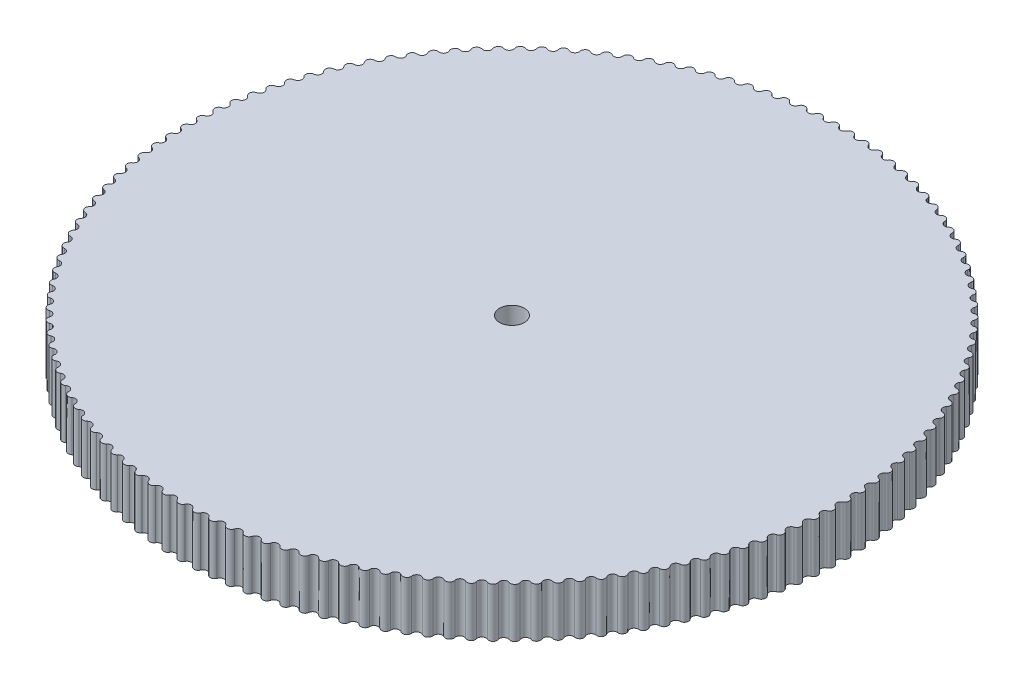
SolidWorks part; units mm, degrees
note: '?' marks a value the reader was unsure of.
ref_plane "Front Plane" through (0, 0, 0) normal (0, 0, 1) x (1, 0, 0)
ref_plane "Top Plane" through (0, 0, 0) normal (0, 1, 0) x (1, 0, 0)
ref_plane "Right Plane" through (0, 0, 0) normal (1, 0, 0) x (0, 0, -1)
sketch "Sketch1" plane through (0, 0, 0) normal (0, 1, 0) x (1, 0, 0)
  line L0 (0, 32.75) -> (0, 33.25) construction
  line L1 (0.7735, 32.7409) -> (0.7853, 33.2407) construction
  line L2 (1.5466, 32.7135) -> (1.5702, 33.2129) construction
  line L3 (0, 33) -> (0, 1.25)
  line L4 (0.059, 1.2486) -> (1.5584, 32.9632)
  circle A0 centre (0, 0) radius 32.75 construction
  arc A1 (0, 33) -> (0.7794, 32.9908) centre (0.3919, 33.1781) ccw
  arc A2 (1.5702, 33.2129) -> (0, 33.25) centre (0, 0) ccw construction
  arc A3 (0.7794, 32.9908) -> (1.5584, 32.9632) centre (1.1627, 32.8022) cw
  arc A4 (0.059, 1.2486) -> (0, 1.25) centre (0, 0) ccw
  point P6 (0, 33)
  point P9 (0.7794, 32.9908)
  dimension "D1" = 65.5
  dimension "D2" = 0.5
  dimension "D3" = 2.5
extrude "Boss-Extrude1" add sketch "Sketch1" along normal blind 5
pattern_circular "CirPattern1" count 133 over 360 about axis through (0, 0, 0) along (0, 1, 0) of "Boss-Extrude1"
ref_axis "Axis1" through (0, 0, 0) along (0, 1, 0)?
sketch "Sketch2" plane through (0, 5, 0) normal (0, 1, 0) x (1, 0, 0)
  line L0 (0, 74.1691) -> (0, -78.0459) construction
  line L1 (4.7625, 3.175) -> (6.6675, 3.175)
  line L2 (4.7625, 3.175) -> (4.7625, -3.175)
  line L3 (4.7625, -3.175) -> (6.6675, -3.175)
  line L4 (6.6675, 3.175) -> (6.6675, -3.175)
  line L5 (-6.6675, 3.175) -> (-6.6675, -3.175)
  line L6 (-4.7625, -3.175) -> (-6.6675, -3.175)
  line L7 (-4.7625, 3.175) -> (-4.7625, -3.175)
  line L8 (-4.7625, 3.175) -> (-6.6675, 3.175)
  point P6 (4.7625, 0)
  point P12 (-4.7625, 0)
  dimension "D1" = 1.905
  dimension "D2" = 6.35
  dimension "D3" = 4.7625
